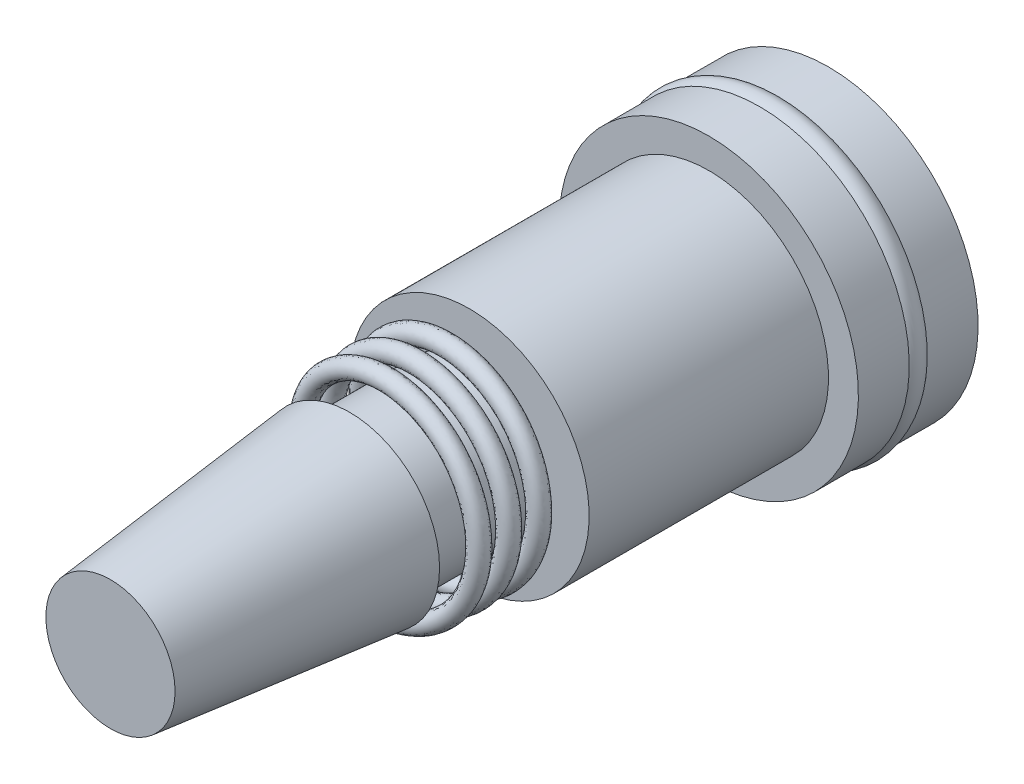
SolidWorks part; units mm, degrees
ref_plane "Front Plane" through (0, 0, 0) normal (0, 0, 1) x (1, 0, 0)
ref_plane "Top Plane" through (0, 0, 0) normal (0, 1, 0) x (1, 0, 0)
ref_plane "Right Plane" through (0, 0, 0) normal (1, 0, 0) x (0, 0, -1)
sketch "Sketch1" plane through (0, 0, 0) normal (0, 0, 1) x (1, 0, 0)
  circle A0 centre (0, 0) radius 0.75
  dimension "D1" = 1.5
extrude "Boss-Extrude1" add sketch "Sketch1" along normal blind 2 draft 6
sketch "Sketch2" plane through (0, 0, 0) normal (0, 0, -1) x (-1, 0, 0)
  circle A0 centre (0, 0) radius 0.625
  dimension "1.25" = 1.25
extrude "Boss-Extrude2" add sketch "Sketch2" along normal blind 1
sketch "Sketch3" plane through (0, 0, -1) normal (0, 0, -1) x (-1, 0, 0)
  circle A0 centre (0, 0) radius 1
  dimension "D1" = 2
extrude "Boss-Extrude3" add sketch "Sketch3" along normal blind 2
sketch "Sketch4" plane through (0, 0, -3) normal (0, 0, -1) x (-1, 0, 0)
  circle A0 centre (0, 0) radius 1.25
  dimension "D1" = 2.5
extrude "Boss-Extrude4" add sketch "Sketch4" along normal blind 1
ref_plane "Plane1" through (0, 0, -4) normal (0, 0, -1) x (-1, 0, 0)
ref_plane "Plane2" through (0, 0, -3.5) normal (0, 0, -1) x (-1, 0, 0)
sketch "Sketch5" plane through (0, 0, -3.5) normal (0, 0, -1) x (-1, 0, 0)
  circle A0 centre (0, 0) radius 1.25 construction
  circle A1 centre (0, 0) radius 1.25
sketch "Sketch6" plane through (0, 0, 0) normal (1, 0, 0) x (0, 0, -1)
  line L2 (3.5, -1.25) -> (3.5, 1.25) construction
  line L3 (3, 1.25) -> (4, 1.25) construction
  circle A0 centre (3.5, 1.15) radius 0.125
  dimension "D1" = 0.25
  dimension "D2" = 0.1
sweep "Cut-Sweep1" cut profiles "Sketch6" path "Sketch5"
sweep "Sweep1" add profiles "Sketch6<2>" path "Sketch5<2>"
sketch "Sketch6<2>" plane through (0, 0, 0) normal (1, 0, 0) x (0, 0, -1) same geometry as "Sketch6"
sketch "Sketch5<2>" plane through (0, 0, -3.5) normal (0, 0, -1) x (-1, 0, 0) same geometry as "Sketch5"
ref_plane "Plane4" through (0, 0, -0.9) normal (0, 0, 1) x (1, 0, 0)
sketch "Sketch9" plane through (0, 0, -0.9) normal (0, 0, 1) x (1, 0, 0)
  circle A0 centre (0, 0) radius 0.81
  dimension "D1" = 1.62
curve "Helix/Spiral2" pitch 0.25 height 0.75 radius 0.81 left hand yes centre (0, 0, -0.9) axis (0, 0, 1) start towards (-1, 0, 0)
ref_plane "Plane5" through (-0.81, 0, -0.9) normal (0, 0.9988, 0.0491) x (1, 0, 0)
sketch "Sketch10" plane through (-0.81, 0, -0.9) normal (0, 0.9988, 0.0491) x (1, 0, 0)
  circle A0 centre (0.0105, 0.0022) radius 0.0777
sweep "Sweep2" add profiles "Sketch10" path "Helix/Spiral2"
